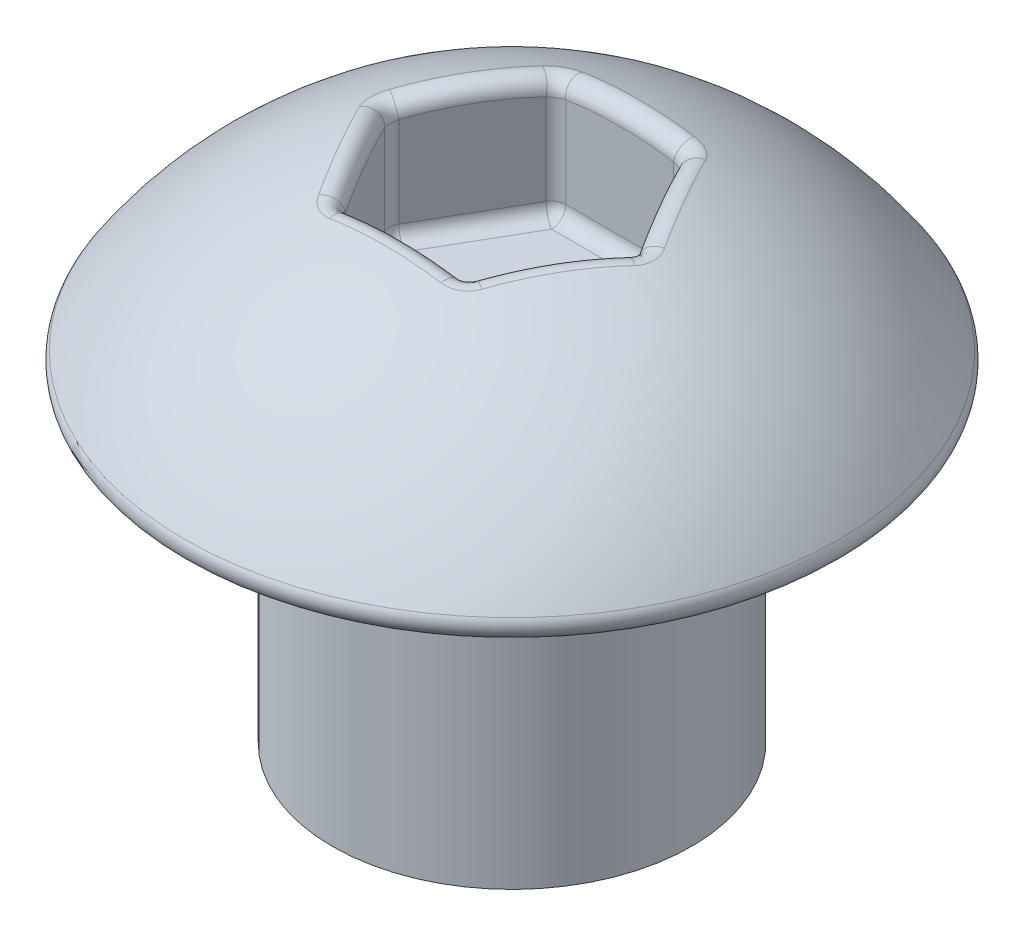
SolidWorks part; units mm, degrees
material "201 Annealed Stainless Steel (SS)"
ref_plane "Front Plane" through (0, 0, 0) normal (0, 0, 1) x (1, 0, 0)
ref_plane "Top Plane" through (0, 0, 0) normal (0, 1, 0) x (1, 0, 0)
ref_plane "Right Plane" through (0, 0, 0) normal (1, 0, 0) x (0, 0, -1)
ref_plane "Top Of head Plane" through (0, 2.75, 0) normal (0, 1, 0) x (1, 0, 0)
sketch "Master Sketch" plane through (0, 0, 0) normal (0, 1, 0) x (1, 0, 0)
  line L1 (0.866, 1.5) -> (-0.866, 1.5)
  line L2 (-0.866, 1.5) -> (-1.7321, 0)
  line L3 (-1.7321, 0) -> (-0.866, -1.5)
  line L4 (-0.866, -1.5) -> (0.866, -1.5)
  line L5 (0.866, -1.5) -> (1.7321, 0)
  line L6 (1.7321, 0) -> (0.866, 1.5)
  circle A0 centre (0, 0) radius 4.75
  circle A1 centre (0, 0) radius 1.5 construction
  circle A2 centre (0, 0) radius 2.5
  dimension "D1" = 9.5
  dimension "D2" = 3
  dimension "D3" = 5
sketch "Threaded Section Stub Sketch" plane through (0, 0, 0) normal (0, 1, 0) x (1, 0, 0)
  circle A0 centre (0, 0) radius 2.5 construction
  circle A1 centre (0, 0) radius 2.5
sketch "Head-Revolve Sketch" plane through (0, 0, 0) normal (0, 0, 1) x (1, 0, 0)
  line L0 (2.5, 0) -> (-2.5, 0) construction
  line L1 (0, 0) -> (-4.75, 0)
  line L2 (0, 0) -> (0, 2.75)
  line L3 (4.75, 0) -> (-4.75, 0) construction
  arc A0 (-4.75, 0) -> (0, 2.75) centre (0, -2.7273) cw
  dimension "D1" = 2.75
revolve "Head Revolve" add sketch "Head-Revolve Sketch" angle 360 about L2
extrude "Threaded Section" add sketch "Threaded Section Stub Sketch" against normal blind 5
sketch "Sketch2" plane through (0, 2.75, 0) normal (0, 1, 0) x (1, 0, 0)
  line L5 (-0.866, 1.5) -> (-1.7321, 0) construction
  line L6 (-0.866, 1.5) -> (-1.7321, 0)
  line L7 (-1.7321, 0) -> (-0.866, -1.5) construction
  line L8 (-0.866, -1.5) -> (0.866, -1.5) construction
  line L9 (0.866, -1.5) -> (1.7321, 0) construction
  line L10 (1.7321, 0) -> (0.866, 1.5) construction
  line L11 (0.866, 1.5) -> (-0.866, 1.5) construction
  line L12 (-1.7321, 0) -> (-0.866, -1.5)
  line L13 (-0.866, -1.5) -> (0.866, -1.5)
  line L14 (0.866, -1.5) -> (1.7321, 0)
  line L15 (1.7321, 0) -> (0.866, 1.5)
  line L16 (0.866, 1.5) -> (-0.866, 1.5)
extrude "Hex Head Cutout" cut sketch "Sketch2" against normal blind 2
fillet "Cosmetic Fillets" radius 0.2 19 edges at (0, 0, -4.75) (-1.299, 2.5406, -0.75) (-1.299, 2.5406, 0.75) (-1.7321, 1.6095, 0) (0, 2.5406, 1.5) (-0.866, 1.6095, 1.5) (1.299, 2.5406, 0.75) (0.866, 1.6095, 1.5) (1.299, 2.5406, -0.75) (1.7321, 1.6095, 0) (0, 2.5406, -1.5) (0.866, 1.6095, -1.5) (-0.866, 1.6095, -1.5) (-1.299, 0.75, -0.75) (0, 0.75, -1.5) (1.299, 0.75, -0.75) (1.299, 0.75, 0.75) (0, 0.75, 1.5) (-1.299, 0.75, 0.75)
chamfer "Cosmetic Chamfers" distance 1 angle 30 1 edges at (0, -5, 2.5) first distance on face at (0, -5, 2.5)
